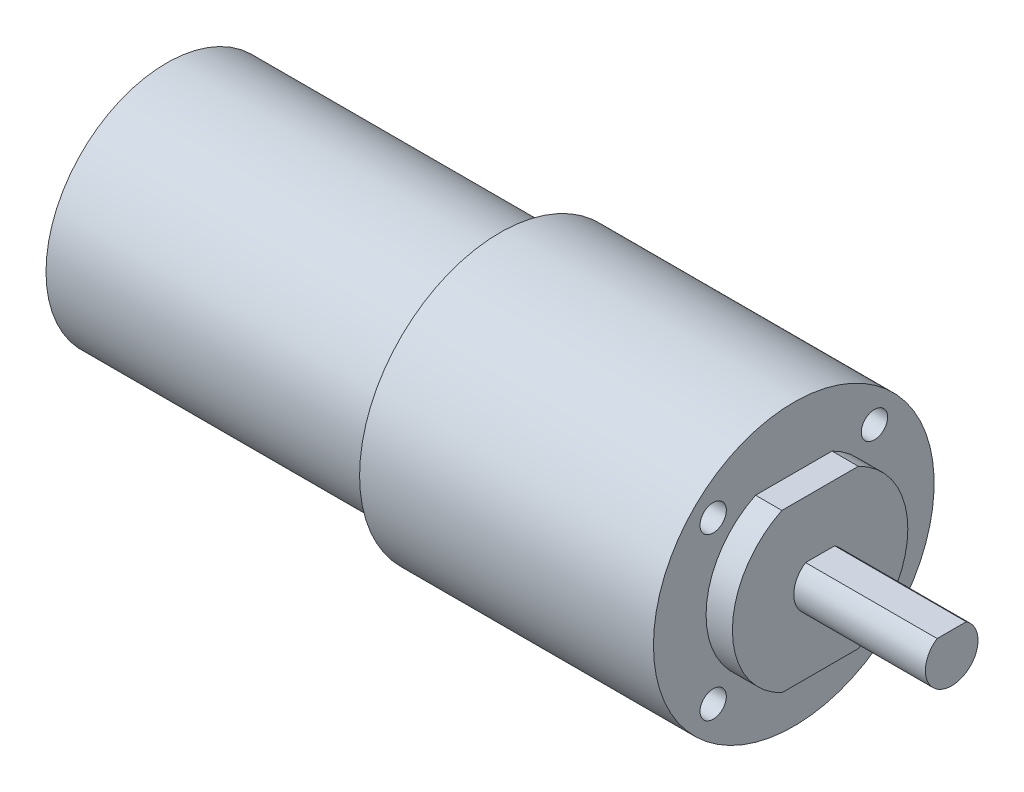
SolidWorks part; units mm, degrees
ref_plane "Front Plane" through (0, 0, 0) normal (0, 0, 1) x (1, 0, 0)
ref_plane "Top Plane" through (0, 0, 0) normal (0, 1, 0) x (1, 0, 0)
ref_plane "Right Plane" through (0, 0, 0) normal (1, 0, 0) x (0, 0, -1)
ref_axis "Axe1" through (-42.475, 0, 0) along (1, 0, 0)
sketch "Esquisse1" plane through (0, 0, 0) normal (0, 0, 1) x (1, 0, 0)
  line L0 (-38, 13.75) -> (0, 13.75)
  line L1 (0, 13.75) -> (0, 16)
  line L2 (0, 16) -> (33.5, 16)
  line L3 (33.5, 16) -> (33.5, 10)
  line L4 (33.5, 10) -> (36.5, 10)
  line L5 (36.5, 10) -> (36.5, 3)
  line L6 (36.5, 3) -> (51.5, 3)
  line L7 (51.5, 3) -> (51.5, 0)
  line L8 (51.5, 0) -> (-38, 0)
  line L9 (-38, 0) -> (-38, 13.75)
  dimension "D1" = 3
  dimension "D2" = 10
  dimension "D3" = 16
  dimension "D4" = 15
  dimension "D5" = 3
  dimension "D6" = 33.5
  dimension "D7" = 38
  dimension "D8" = 13.75
revolve "Révolution1" add sketch "Esquisse1" angle 360 about axis through (-42.475, 0, 0) along (1, 0, 0)
sketch "Esquisse2" plane through (36.5, 0, 0) normal (1, 0, 0) x (0, 0, -1)
  line L0 (-4.3589, 9) -> (4.3589, 9)
  line L1 (-4.3589, -9) -> (4.3589, -9)
  circle A0 centre (0, 0) radius 10 construction
  circle A1 centre (0, 0) radius 10 construction
  arc A2 (-4.3589, 9) -> (4.3589, 9) centre (0, 0) cw
  arc A3 (4.3589, -9) -> (-4.3589, -9) centre (0, 0) cw
  dimension "D1" = 9
  dimension "D2" = 9
extrude "MeplatFixing" cut sketch "Esquisse2" against normal up to surface (3 mm away) up to face at (33.5, 0, 16)
sketch "Esquisse3" plane through (51.5, 0, 0) normal (1, 0, 0) x (0, 0, -1)
  line L0 (-1.6583, 2.5) -> (1.6583, 2.5)
  circle A0 centre (0, 0) radius 3 construction
  arc A1 (-1.6583, 2.5) -> (1.6583, 2.5) centre (0, 0) cw
  dimension "D1" = 2.5
extrude "MeplatRotor" cut sketch "Esquisse3" against normal up to surface (15 mm away) up to face at (36.5, 0, 0)
sketch "Esquisse4" plane through (33.5, 0, 0) normal (1, 0, 0) x (0, 0, -1)
  line L0 (0, 0) -> (22.8047, 0) construction
  line L1 (0, 0) -> (9.1924, 9.1924) construction
  circle A0 centre (9.1924, 9.1924) radius 1.5
  dimension "D1" = 3
  dimension "D2" = 13
  dimension "D3" = 45
extrude "FixingHole" cut sketch "Esquisse4" against normal blind 5
pattern_circular "FixingHoleCircularRepetition" count 4 over 360 about axis through (-42.475, 0, 0) along (1, 0, 0) of "FixingHole"
